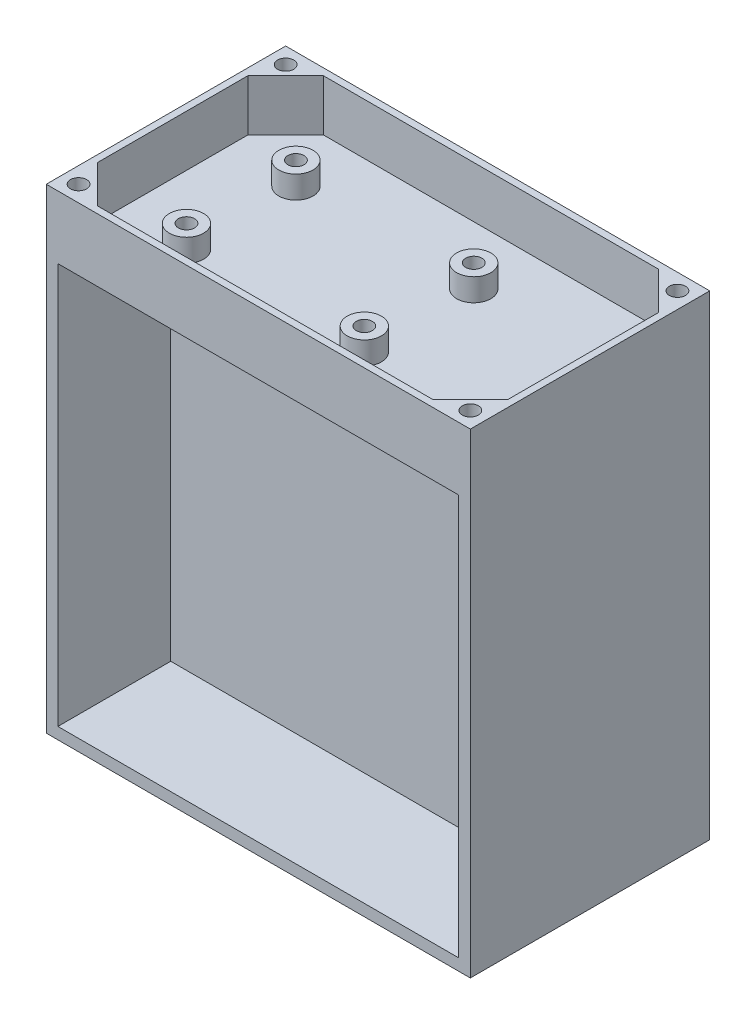
SolidWorks part; units mm, degrees
ref_plane "Front Plane" through (0, 0, 0) normal (0, 0, 1) x (1, 0, 0)
ref_plane "Top Plane" through (0, 0, 0) normal (0, 1, 0) x (1, 0, 0)
ref_plane "Right Plane" through (0, 0, 0) normal (1, 0, 0) x (0, 0, -1)
sketch "Sketch1" plane through (0, 0, 0) normal (0, 1, 0) x (1, 0, 0)
  line L1 (0, 0) -> (78.74, 0)
  line L2 (0, 0) -> (0, 44.45)
  line L3 (0, 44.45) -> (78.74, 44.45)
  line L4 (78.74, 0) -> (78.74, 44.45)
  dimension "D1" = 78.74
  dimension "D2" = 44.45
extrude "Boss-Extrude1" add sketch "Sketch1" along normal blind 78.74
sketch "Sketch2" plane through (0, 0, 0) normal (0, 0, 1) x (1, 0, 0)
  line L0 (0, 78.74) -> (0, 0) construction
  line L1 (2.159, 2.159) -> (76.581, 2.159)
  line L2 (2.159, 2.159) -> (2.159, 76.581)
  line L3 (2.159, 76.581) -> (76.581, 76.581)
  line L4 (76.581, 2.159) -> (76.581, 76.581)
  line L5 (78.74, 78.74) -> (78.74, 0) construction
  line L6 (0, 0) -> (78.74, 0) construction
  line L7 (0, 78.74) -> (78.74, 78.74) construction
  dimension "D1" = 2.159
  dimension "D2" = 2.159
  dimension "D3" = 2.159
  dimension "D4" = 2.159
extrude "Cut-Extrude1" cut sketch "Sketch2" against normal blind 20.955
sketch "Sketch3" plane through (0, 0, -44.45) normal (0, 0, -1) x (-1, 0, 0)
  line L1 (-76.581, 2.159) -> (-2.159, 2.159)
  line L2 (-76.581, 2.159) -> (-76.581, 76.581)
  line L3 (-76.581, 76.581) -> (-2.159, 76.581)
  line L4 (-2.159, 2.159) -> (-2.159, 76.581)
  line L8 (0, 78.74) -> (0, 0) construction
  line L9 (-78.74, 0) -> (0, 0) construction
  line L10 (-78.74, 78.74) -> (-78.74, 0) construction
  line L11 (-78.74, 78.74) -> (0, 78.74) construction
  dimension "D1" = 2.159
  dimension "D2" = 2.159
  dimension "D3" = 2.159
  dimension "D4" = 2.159
extrude "Cut-Extrude2" cut sketch "Sketch3" against normal blind 20.955
sketch "Sketch4" plane through (0, 78.74, 0) normal (0, 1, 0) x (1, 0, 0)
  line L1 (0, 0) -> (78.74, 0)
  line L2 (0, 0) -> (0, 44.45)
  line L3 (0, 44.45) -> (78.74, 44.45)
  line L4 (78.74, 0) -> (78.74, 44.45)
  line L5 (1.27, 1.27) -> (77.47, 1.27)
  line L6 (1.27, 1.27) -> (1.27, 43.18)
  line L7 (1.27, 43.18) -> (77.47, 43.18)
  line L8 (77.47, 1.27) -> (77.47, 43.18)
  dimension "D1" = 1.27
  dimension "D2" = 1.27
  dimension "D3" = 1.27
  dimension "D4" = 1.27
extrude "Boss-Extrude2" add sketch "Sketch4" along normal blind 9.525
sketch "Sketch5" plane through (0, 78.74, 0) normal (0, 1, 0) x (1, 0, 0)
  line L0 (0, 0) -> (78.74, 0) construction
  line L2 (1.27, 43.18) -> (1.27, 1.27) construction
  circle A0 centre (13.97, 12.065) radius 3.175
  circle A1 centre (13.97, 12.065) radius 1.5
  circle A2 centre (13.97, 32.385) radius 3.175
  circle A3 centre (13.97, 32.385) radius 1.5
  circle A4 centre (46.99, 32.385) radius 3.175
  circle A5 centre (46.99, 32.385) radius 1.5
  circle A6 centre (46.99, 12.065) radius 3.175
  circle A7 centre (46.99, 12.065) radius 1.5
  point P12 (0, 0)
  point P13 (0, 0)
  point P14 (0, 0)
  point P15 (0, 0)
  point P16 (0, 0)
  point P17 (0, 0)
  point P22 (0, 0)
  dimension "D4" = 6.35
  dimension "D5" = 6.35
  dimension "D6" = 6.35
  dimension "D7" = 6.35
  dimension "D8" = 3
  dimension "D9" = 3
  dimension "D10" = 3
  dimension "D11" = 3
  dimension "D1" = 20.32
  dimension "D2" = 12.065
  dimension "D3" = 33.02
  dimension "D12" = 12.7
extrude "Boss-Extrude3" add sketch "Sketch5" along normal blind 4.191
extrude "Cut-Extrude3" cut sketch "Sketch5<2>" against normal up to next contours A1 | A3 | A5 | A7 region at (13.97, 78.74, -12.065) region at (13.97, 78.74, -32.385) region at (46.99, 78.74, -32.385) region at (46.99, 78.74, -12.065)
sketch "Sketch5<2>" plane through (0, 78.74, 0) normal (0, 1, 0) x (1, 0, 0) same geometry as "Sketch5"
chamfer "Chamfer1" distance 6.985 angle 45 4 edges at (77.47, 83.5025, -1.27) (77.47, 83.5025, -43.18) (1.27, 83.5025, -1.27) (1.27, 83.5025, -43.18)
sketch "Sketch6" plane through (0, 88.265, 0) normal (0, 1, 0) x (1, 0, 0)
  line L0 (0, 0) -> (78.74, 0) construction
  line L1 (78.74, 44.45) -> (0, 44.45) construction
  line L2 (78.74, 0) -> (78.74, 44.45) construction
  line L3 (0, 44.45) -> (0, 0) construction
  circle A0 centre (3, 3) radius 1.5
  circle A1 centre (3, 41.45) radius 1.5
  circle A2 centre (75.74, 41.45) radius 1.5
  circle A3 centre (75.74, 3) radius 1.5
  point P8 (0, 0)
  point P9 (0, 0)
  point P10 (0, 0)
  point P11 (0, 0)
  dimension "D1" = 3
  dimension "D2" = 3
  dimension "D3" = 3
  dimension "D4" = 3
  dimension "D5" = 3
  dimension "D6" = 3
  dimension "D7" = 3
  dimension "D8" = 3
extrude "Cut-Extrude4" cut sketch "Sketch6" against normal up to surface (11.684 mm away) up to face at (46.99, 76.581, -10.565)
